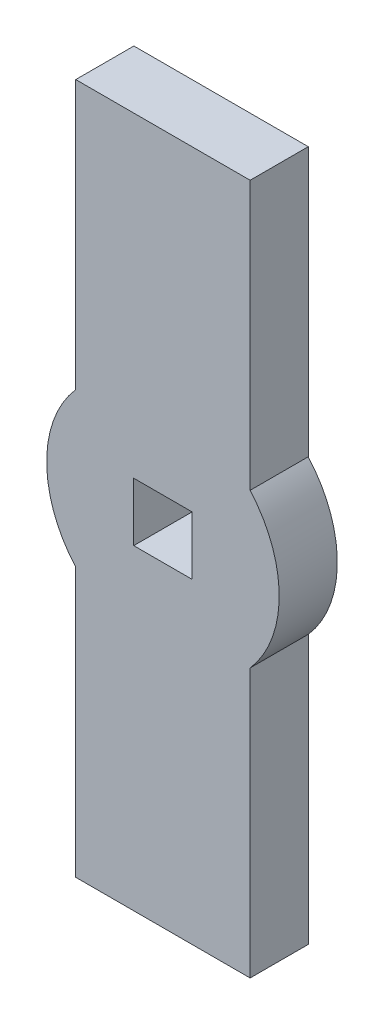
SolidWorks part; units mm, degrees
ref_plane "Front Plane" through (0, 0, 0) normal (0, 0, 1) x (1, 0, 0)
ref_plane "Top Plane" through (0, 0, 0) normal (0, 1, 0) x (1, 0, 0)
ref_plane "Right Plane" through (0, 0, 0) normal (1, 0, 0) x (0, 0, -1)
sketch "Sketch2" plane through (0, 0, 0) normal (0, 0, 1) x (1, 0, 0)
  line L0 (0, -167.7125) -> (0, 37.7373) construction
  line L5 (-9.525, 8.4003) -> (-9.525, 37.7373)
  line L6 (-9.525, 37.7373) -> (9.525, 37.7373)
  line L7 (9.525, 37.7373) -> (9.525, 8.4003)
  line L8 (-74.2931, 0) -> (71.2723, 0) construction
  line L9 (9.525, -37.7373) -> (9.525, -8.4003)
  line L15 (-9.525, -37.7373) -> (9.525, -37.7373)
  line L16 (-9.525, -8.4003) -> (-9.525, -37.7373)
  circle A1 centre (0, 0) radius 2.032
  circle A4 centre (0, 0) radius 12.7 construction
  arc A5 (-9.525, 8.4003) -> (-9.525, -8.4003) centre (0, 0) ccw
  arc A9 (9.525, -8.4003) -> (9.525, 8.4003) centre (0, 0) ccw
  dimension "D4" = 4.064
  dimension "D1" = 25.4
  dimension "D5" = 29.337
  dimension "D6" = 19.05
extrude "Boss-Extrude1" add sketch "Sketch2" along normal blind 6.35
sketch "Sketch3" plane through (0, 0, 0) normal (0, 0, -1) x (-1, 0, 0)
  line L1 (-3.19, 3.19) -> (3.19, 3.19)
  line L2 (-3.19, 3.19) -> (-3.19, -3.19)
  line L3 (-3.19, -3.19) -> (3.19, -3.19)
  line L4 (3.19, 3.19) -> (3.19, -3.19)
  line L5 (-3.19, 3.19) -> (3.19, -3.19) construction
  line L6 (-3.19, -3.19) -> (3.19, 3.19) construction
  point P0 (0, 0)
  dimension "D1" = 6.38
  dimension "D2" = 6.38
extrude "Cut-Extrude1" cut sketch "Sketch3" against normal through all
